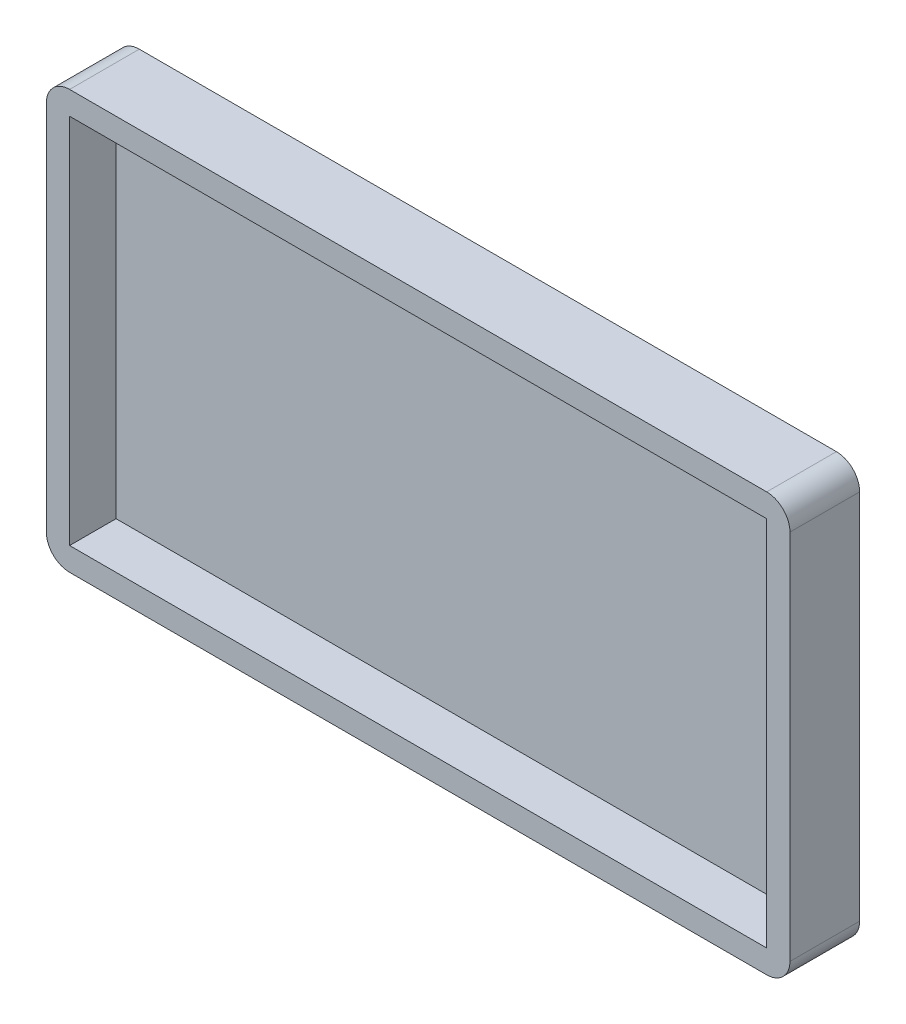
SolidWorks part; units mm, degrees
ref_plane "Front Plane" through (0, 0, 0) normal (0, 0, 1) x (1, 0, 0)
ref_plane "Top Plane" through (0, 0, 0) normal (0, 1, 0) x (1, 0, 0)
ref_plane "Right Plane" through (0, 0, 0) normal (1, 0, 0) x (0, 0, -1)
sketch "Sketch1" plane through (0, 0, 0) normal (0, 0, 1) x (1, 0, 0)
  line L1 (0, 0) -> (64, 0)
  line L2 (0, 0) -> (0, -36)
  line L3 (0, -36) -> (64, -36)
  line L4 (64, 0) -> (64, -36)
  dimension "D1" = 36
  dimension "D2" = 64
extrude "Boss-Extrude1" add sketch "Sketch1" along normal blind 6
fillet "Fillet1" radius 2 4 edges at (0, -36, 3) (64, -36, 3) (64, 0, 3) (0, 0, 3)
sketch "Sketch2" plane through (0, 0, 6) normal (0, 0, 1) x (1, 0, 0)
  line L0 (62, 0) -> (2, 0) construction
  line L1 (2, -2) -> (62, -2)
  line L2 (2, -2) -> (2, -34)
  line L3 (2, -34) -> (62, -34)
  line L4 (62, -2) -> (62, -34)
  line L5 (0, -2) -> (0, -34) construction
  line L6 (64, -34) -> (64, -2) construction
  line L7 (2, -36) -> (62, -36) construction
  dimension "D1" = 2
  dimension "D2" = 2
  dimension "D3" = 2
  dimension "D4" = 2
extrude "Cut-Extrude1" cut sketch "Sketch2" against normal blind 4
